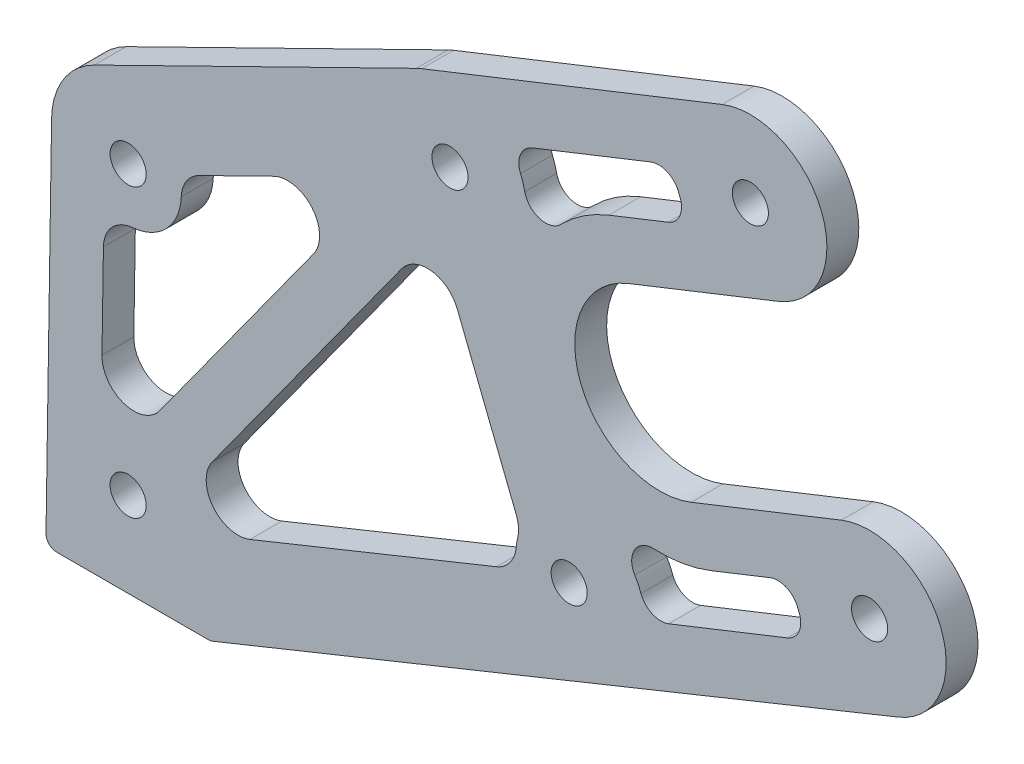
SolidWorks part; units mm, degrees
ref_plane "Front Plane" through (0, 0, 0) normal (0, 0, 1) x (1, 0, 0)
ref_plane "Top Plane" through (0, 0, 0) normal (0, 1, 0) x (1, 0, 0)
ref_plane "Right Plane" through (0, 0, 0) normal (1, 0, 0) x (0, 0, -1)
sketch "Sketch1" plane through (0, 0, 0) normal (0, 0, 1) x (1, 0, 0)
  line L0 (0, 0) -> (0, 27) construction
  line L1 (-7.745, -8) -> (7.745, -8)
  line L2 (0, 0) -> (0, -8) construction
  line L3 (0, 13.5) -> (50.0175, 33.3497) construction
  line L4 (50.0175, 33.3497) -> (58.5403, 53.0883) construction
  line L5 (7.745, -8) -> (72.4546, 18.1487)
  line L6 (52.9684, 25.9139) -> (67.0992, 31.5217)
  line L7 (47.0665, 40.7856) -> (61.1972, 46.3934)
  line L8 (27.622, 48.5674) -> (55.8834, 59.7832)
  line L9 (-3.1755, 33.465) -> (27.1034, 48.3376)
  line L10 (-7.745, -8) -> (-7.2019, 27.1114)
  circle A0 centre (50.0175, 33.3497) radius 21.5 construction
  arc A1 (52.9684, 25.9139) -> (47.0665, 40.7856) centre (50.0175, 33.3497) cw
  arc A2 (67.0992, 31.5217) -> (72.4546, 18.1487) centre (69.756, 24.8269) cw
  arc A3 (61.1972, 46.3934) -> (55.8834, 59.7832) centre (58.5403, 53.0883) ccw
  arc A4 (27.622, 48.5674) -> (27.1034, 48.3376) centre (30.2789, 41.8726) ccw
  arc A5 (-7.2019, 27.1114) -> (-3.1755, 33.465) centre (0, 27) cw
  point P9 (58.5403, 53.0883)
  point P14 (30.2789, 41.8726)
  point P15 (41.4946, 13.6112)
  point P16 (69.756, 24.8269)
  point P17 (50.0175, 33.3497)
  point P27 (0, 0)
  point P28 (0, 0)
  point P29 (0, 0)
  point P30 (0, 0)
  point P31 (0, 0)
  point P32 (0, 0)
  dimension "D4" = 43
  dimension "D5" = 60.1162
  dimension "D9" = 8
  dimension "D1" = 27
  dimension "D2" = 15.49
  dimension "D3" = 8
  dimension "D6" = 50.4189
  dimension "D7" = 135
  dimension "D8" = 4
extrude "Boss-Extrude1" add sketch "Sketch1" along normal blind 3
sketch "Sketch2" plane through (0, 0, 0) normal (0, 0, 1) x (1, 0, 0)
  point P0 (58.5403, 53.0883)
  point P2 (69.756, 24.8269)
  point P4 (41.4946, 13.6112)
  point P6 (30.2789, 41.8726)
  point P8 (0, 27)
  point P10 (0, 0)
  point P12 (0, 0)
hole_wizard "M3 Clearance Hole1" positions "Sketch2" profile "Sketch3" hole size "M3" standard "ANSI Metric" end condition through all
sketch "Sketch3" plane through (58.5403, 53.0883, 0) normal (1, 0, 0) x (0, 1, 0)
  line L0 (0, 0) -> (0, 3)
  line L1 (0, 3) -> (1.7, 3)
  line L2 (1.7, 3) -> (1.7, 0)
  line L5 (1.7, 0) -> (0, 0)
  line L11 (0, -6.35) -> (0, 107.95) construction
  dimension "Thru Hole Dia." = 3.4
  dimension "Thru Hole Depth" = 3
fillet "Fillet1" radius 1 2 edges at (7.745, -8, 1.5) (-7.745, -8, 1.5)
sketch "Sketch4" plane through (0, 0, 0) normal (0, 0, -1) x (-1, 0, 0)
  line L0 (-30.2789, 41.8726) -> (0, 0) construction
  line L1 (0, 0) -> (-41.4946, 13.6112) construction
  line L2 (-41.4946, 13.6112) -> (-30.2789, 41.8726) construction
  line L3 (-30.2789, 41.8726) -> (0, 27) construction
  line L4 (0, 27) -> (0, 0) construction
  line L5 (-36.6655, 12.3151) -> (-1.8034, -1.7725)
  line L6 (-7.9252, -7.9272) -> (-72.4546, 18.1487) construction
  line L7 (-1.8034, -1.7725) -> (-28.9409, 35.7558)
  line L8 (-28.9409, 35.7558) -> (-36.9243, 15.639)
  line L9 (2.6105, 0.6564) -> (-24.4983, 38.145)
  line L10 (2.6105, 0.6564) -> (2.2719, 22.546)
  line L11 (7.2019, 27.1114) -> (7.7293, -6.9845) construction
  line L12 (-24.4983, 38.145) -> (-4.7819, 28.4606)
  line L13 (-27.1034, 48.3376) -> (3.1755, 33.465) construction
  line L14 (-62.0168, 19.3856) -> (-50.8589, 14.9575)
  line L15 (-60.3918, 23.4805) -> (-54.8128, 21.2665)
  line L16 (-67.0992, 31.5217) -> (-52.9684, 25.9139) construction
  line L17 (-69.756, 24.8269) -> (-41.4946, 13.6112) construction
  line L18 (-69.756, 24.8269) -> (-58.5403, 53.0883) construction
  line L19 (-50.0175, 33.3497) -> (-64.1482, 38.9576) construction
  line L20 (-58.5403, 53.0883) -> (-30.2789, 41.8726) construction
  line L22 (-49.176, 51.7419) -> (-38.0181, 47.3138)
  line L23 (-50.8011, 47.647) -> (-45.2222, 45.433)
  arc A0 (-36.9243, 15.639) -> (-36.6655, 12.3151) centre (-41.4946, 13.6112) cw
  arc A3 (2.2719, 22.546) -> (-4.7819, 28.4606) centre (0, 27) cw
  arc A5 (-52.9684, 25.9139) -> (-47.0665, 40.7856) centre (-50.0175, 33.3497) ccw construction
  arc A6 (-52.9684, 25.9139) -> (-47.0665, 40.7856) centre (-50.0175, 33.3497) ccw construction
  arc A7 (-63.1214, 22.0231) -> (-63.0043, 22.3182) centre (-69.756, 24.8269) ccw
  arc A8 (-48.2464, 16.1199) -> (-47.6627, 17.3307) centre (-41.4946, 13.6112) cw
  arc A9 (-67.0992, 31.5217) -> (-72.4546, 18.1487) centre (-69.756, 24.8269) ccw construction
  arc A11 (-48.2464, 16.1199) -> (-50.8589, 14.9575) centre (-50.1212, 16.8165) cw
  arc A12 (-63.1214, 22.0231) -> (-62.0168, 19.3856) centre (-61.2791, 21.2446) ccw
  arc A13 (-63.0043, 22.3182) -> (-60.3918, 23.4805) centre (-61.1295, 21.6216) cw
  arc A14 (-51.9057, 50.2845) -> (-50.8011, 47.647) centre (-50.0634, 49.506) ccw
  arc A15 (-51.7886, 50.5796) -> (-49.176, 51.7419) centre (-49.9138, 49.883) cw
  arc A16 (-36.9136, 44.6764) -> (-38.0181, 47.3138) centre (-38.7559, 45.4549) ccw
  arc A18 (-36.9136, 44.6764) -> (-37.319, 43.3948) centre (-30.2789, 41.8726) ccw
  arc A19 (-51.7886, 50.5796) -> (-51.9057, 50.2845) centre (-58.5403, 53.0883) cw
  arc A20 (-54.8128, 21.2665) -> (-49.461, 20.3616) centre (-50.0175, 33.3497) ccw
  arc A22 (-47.6627, 17.3307) -> (-49.461, 20.3616) centre (-49.3754, 18.3635) ccw
  arc A25 (-37.319, 43.3948) -> (-40.7063, 42.4218) centre (-39.2738, 43.8175) cw
  arc A26 (-45.2222, 45.433) -> (-40.7063, 42.4218) centre (-50.0175, 33.3497) cw
  point P30 (-47.0665, 18.1562)
  point P37 (-51.0157, 20.8219)
  point P63 (-47.1581, 20.7938)
  point P64 (0, 0)
  point P65 (-47.6097, 17.4172)
  point P66 (-47.0823, 18.123)
  dimension "D1" = 5
  dimension "D8" = 2
  dimension "D9" = 2
  dimension "D2" = 8
  dimension "D3" = 5
  dimension "D4" = 8
  dimension "D5" = 5
  dimension "D6" = 3.5
  dimension "D7" = 5
extrude "Cut-Extrude1" cut sketch "Sketch4" against normal through all
fillet "Fillet2" radius 3 8 edges at (-2.2719, 22.546, 1.5) (4.7819, 28.4606, 1.5) (-2.6105, 0.6564, 1.5) (24.4983, 38.145, 1.5) (28.9409, 35.7558, 1.5) (36.9243, 15.639, 1.5) (36.6655, 12.3151, 1.5) (1.8034, -1.7725, 1.5)
